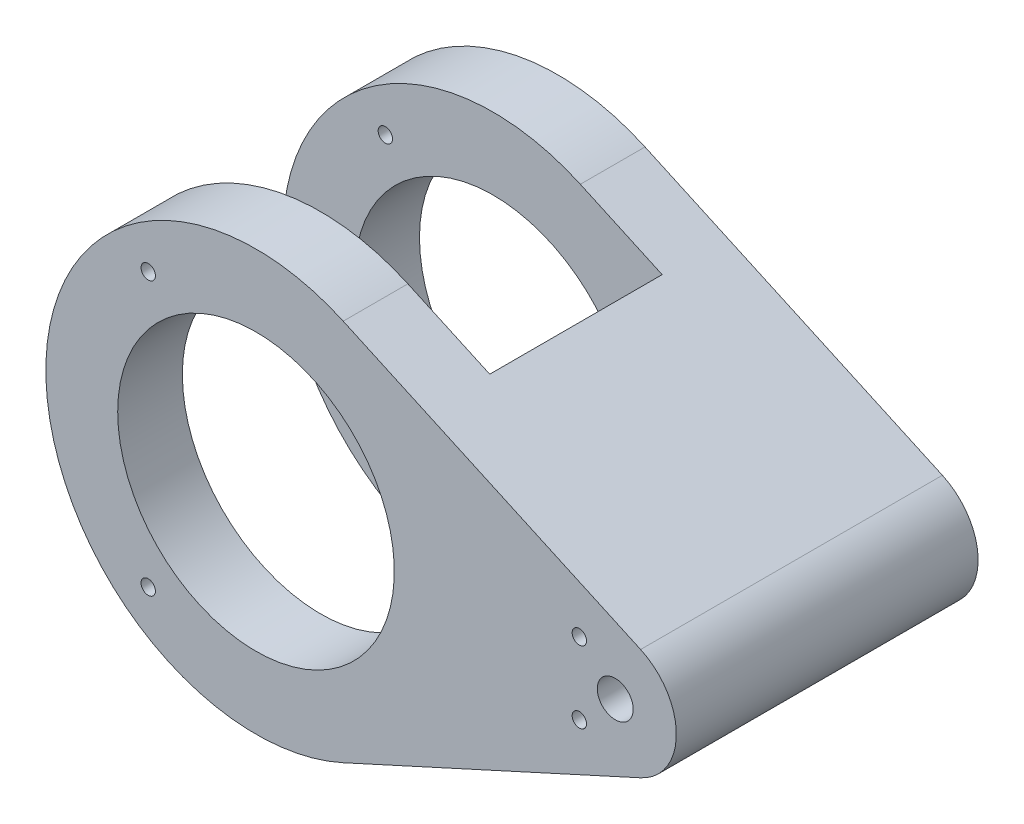
SolidWorks part; units mm, degrees
ref_plane "Face" through (0, 0, 0) normal (0, 0, 1) x (1, 0, 0)
ref_plane "Dessus" through (0, 0, 0) normal (0, 1, 0) x (1, 0, 0)
ref_plane "Droite" through (0, 0, 0) normal (1, 0, 0) x (0, 0, -1)
sketch "Esquisse1" plane through (0, 0, 0) normal (0, 0, 1) x (1, 0, 0)
  line L0 (50, 0) -> (0, 0) construction
  line L1 (12.1387, 26.6123) -> (53.5275, 7.7335)
  line L2 (-29.25, 0) -> (0, 0) construction
  line L3 (12.1388, -26.6123) -> (53.5275, -7.7335)
  line L4 (58.5, 0) -> (50, 0) construction
  circle A0 centre (0, 0) radius 19.25
  circle A1 centre (50, 0) radius 2.5
  arc A2 (12.1387, 26.6123) -> (12.1388, -26.6123) centre (0, 0) ccw
  arc A3 (53.5275, 7.7335) -> (53.5275, -7.7335) centre (50, 0) cw
  dimension "D1" = 38.5
  dimension "D2" = 5
  dimension "D4" = 10
  dimension "D5" = 6
  dimension "D3" = 50
extrude "Boss.-Extru.1" add sketch "Esquisse1" along normal blind 42
sketch "Esquisse2" plane through (5.2188, 0, 0) normal (0, 1, 0) x (1, 0, 0)
  line L0 (18.3087, -33) -> (-71.6913, -33)
  line L1 (-71.6913, -33) -> (-71.6913, -9)
  line L2 (48.3087, -21) -> (6.9199, -21) construction
  line L3 (48.3087, -42) -> (48.3087, 0) construction
  line L4 (6.9199, -42) -> (6.9199, 0) construction
  line L5 (48.3087, -42) -> (6.9199, -42) construction
  line L6 (18.3087, -33) -> (18.3087, -9)
  line L7 (18.3087, -9) -> (-71.6913, -9)
  point P13 (18.3087, -21)
  point P14 (-71.6913, -21)
  dimension "D1" = 9
  dimension "D2" = 90
  dimension "D3" = 30
extrude "Enlèv. mat.-Extru.1" cut sketch "Esquisse2" against normal through all both and the other way through all
sketch "Esquisse3" plane through (0, 0, 42) normal (0, 0, 1) x (1, 0, 0)
  line L0 (50, 0) -> (45, 0) construction
  line L1 (45, 0) -> (45, 5) construction
  line L2 (-15, 19) -> (-15, 0) construction
  line L3 (-15, 0) -> (50, 0) construction
  circle A0 centre (45, 5) radius 1
  circle A1 centre (45, -5) radius 1
  circle A2 centre (-15, 19) radius 1
  circle A3 centre (-15, -19) radius 1
  dimension "D1" = 2
  dimension "D2" = 5
  dimension "D3" = 5
  dimension "D4" = 65
  dimension "D5" = 19
extrude "Enlèv. mat.-Extru.2" cut sketch "Esquisse3" against normal up to vertex (42 mm away) up to point (53.5275, 7.7335, 0)
